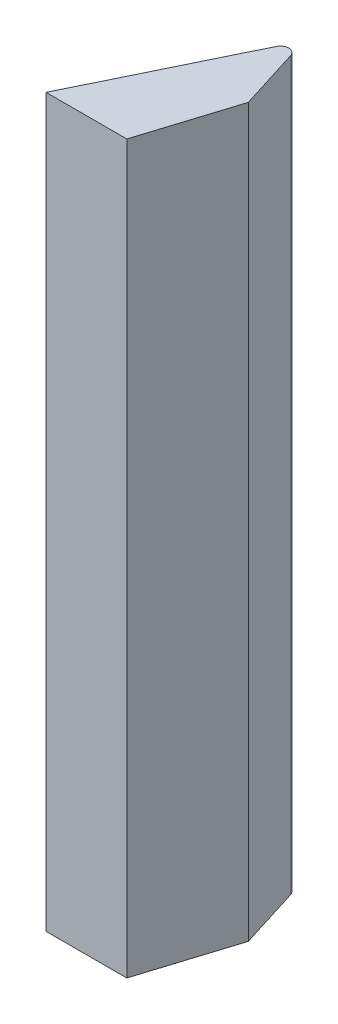
SolidWorks part; units mm, degrees
ref_plane "Спереди" through (0, 0, 0) normal (0, 0, 1) x (1, 0, 0)
ref_plane "Сверху" through (0, 0, 0) normal (0, 1, 0) x (1, 0, 0)
ref_plane "Справа" through (0, 0, 0) normal (1, 0, 0) x (0, 0, -1)
sketch "Эскиз1" plane through (0, 0, 0) normal (0, 1, 0) x (1, 0, 0)
  line L0 (-50, 0) -> (0, 0)
  line L1 (0, 0) -> (17.9839, 57.2414)
  line L2 (17.9839, 57.2414) -> (6.0322, 95.4141)
  line L3 (-3.2354, 96.1078) -> (-50, 0)
  arc A3 (6.0322, 95.4141) -> (-3.2354, 96.1078) centre (1.2606, 93.9202) ccw
  point P0 (-48.7034, 0.9456)
  point P9 (0, 0)
  point P12 (17.9839, 57.2414)
  dimension "D2" = 5
extrude "Бобышка-Вытянуть1" add sketch "Эскиз1" along normal blind 450
